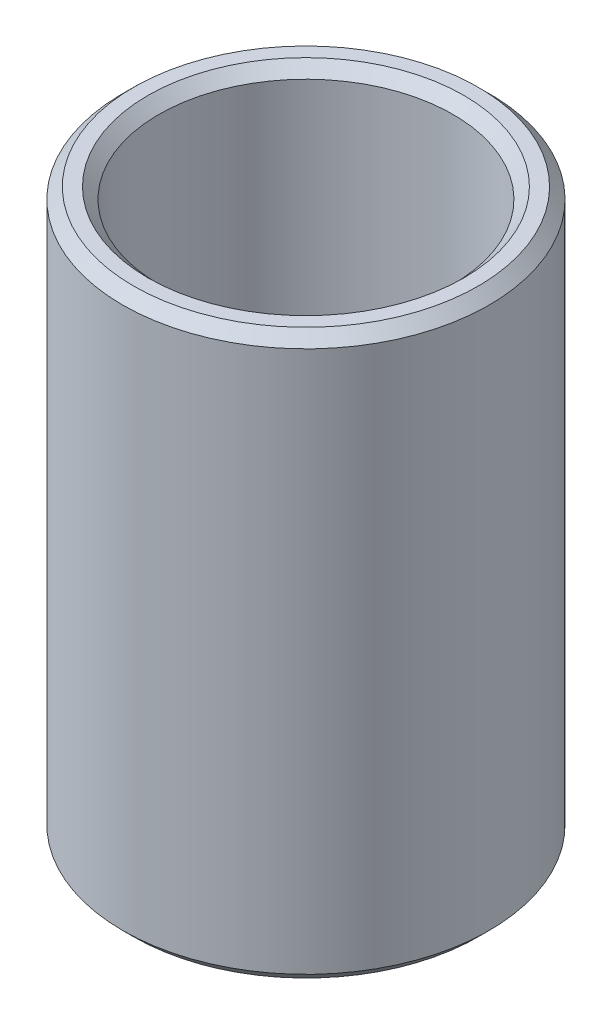
SolidWorks part; units mm, degrees
ref_plane "Front Plane" through (0, 0, 0) normal (0, 0, 1) x (1, 0, 0)
ref_plane "Top Plane" through (0, 0, 0) normal (0, 1, 0) x (1, 0, 0)
ref_plane "Right Plane" through (0, 0, 0) normal (1, 0, 0) x (0, 0, -1)
sketch "Sketch1" plane through (0, 0, 0) normal (0, 1, 0) x (1, 0, 0)
  circle A0 centre (0, 0) radius 15
  dimension "SLEEVE_OD" = 30
extrude "Boss-Extrude1" add sketch "Sketch1" along normal blind 46.1409
sketch "Sketch2" plane through (0, 0, 0) normal (0, 1, 0) x (1, 0, 0)
  circle A0 centre (0, 0) radius 12.0413
  dimension "BORE_D" = 24.0826
extrude "Cut-Extrude1" cut sketch "Sketch2" along normal through all
chamfer "Chamfer1" distance 0.8962 angle 45 4 edges at (0, 46.1409, 12.0413) (0, 0, 12.0413) (0, 0, 15) (0, 46.1409, 15)
